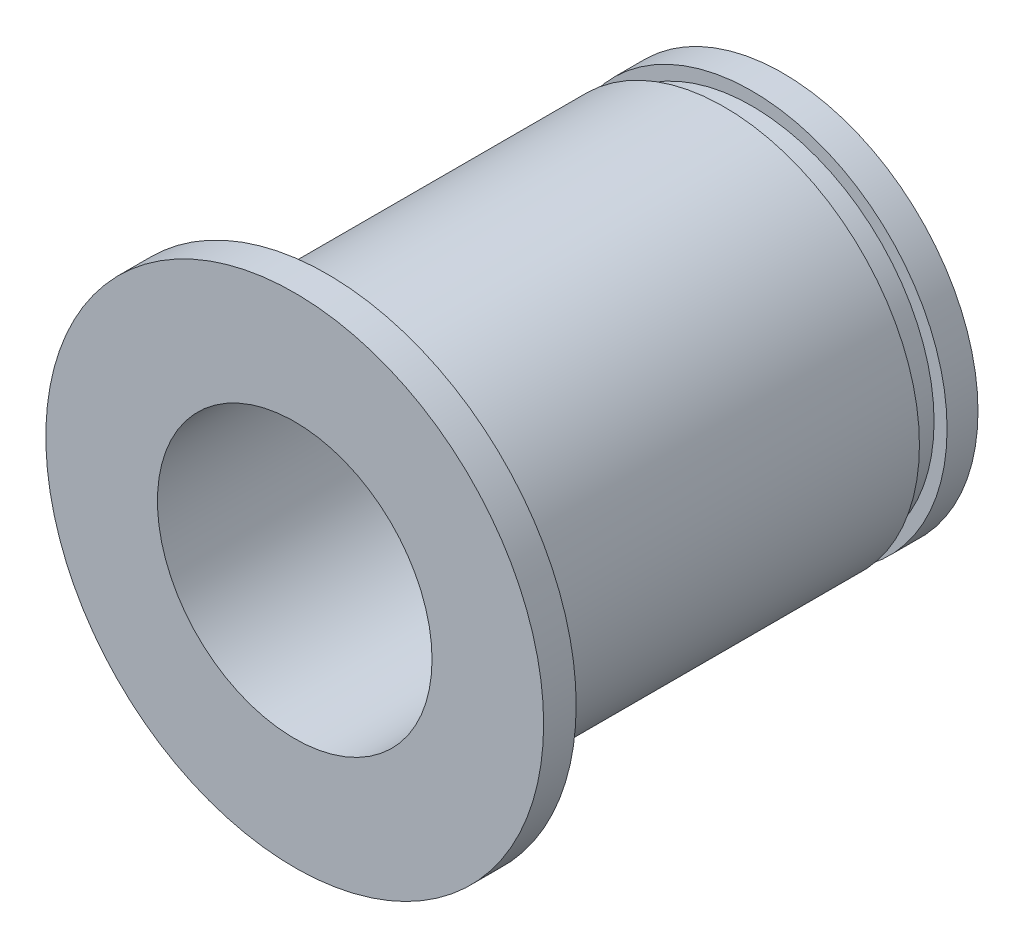
SolidWorks part; units mm, degrees
ref_plane "Front Plane" through (0, 0, 0) normal (0, 0, 1) x (1, 0, 0)
ref_plane "Top Plane" through (0, 0, 0) normal (0, 1, 0) x (1, 0, 0)
ref_plane "Right Plane" through (0, 0, 0) normal (1, 0, 0) x (0, 0, -1)
sketch "S01 - Ground guide bore and body" plane through (0, 0, 0) normal (0, 0, 1) x (1, 0, 0)
  circle A0 centre (0, 0) radius 6
  circle A1 centre (0, 0) radius 4.22
  dimension "D1" = 8.44
  dimension "D2" = 12
extrude "01 - Ground guide bore and body" add sketch "S01 - Ground guide bore and body" along normal blind 14 from offset 2 offset against normal yes
sketch "S02 - Outboard flange" plane through (0, 0, 0) normal (0, 0, 1) x (1, 0, 0)
  circle A0 centre (0, 0) radius 7.65
  circle A1 centre (0, 0) radius 4.22
  dimension "D1" = 8.44
  dimension "D2" = 15.3
extrude "02 - Outboard flange" add sketch "S02 - Outboard flange" along normal blind 1 from offset 12
sketch "S03 - External retaining ring groove" plane through (0, 0, 0) normal (0, 0, 1) x (1, 0, 0)
  circle A0 centre (0, 0) radius 6.1
  circle A1 centre (0, 0) radius 5.6
  dimension "D1" = 11.2
  dimension "D2" = 12.2
extrude "03 - External retaining ring groove" cut sketch "S03 - External retaining ring groove" along normal blind 0.85 from offset 1.05 offset against normal yes
